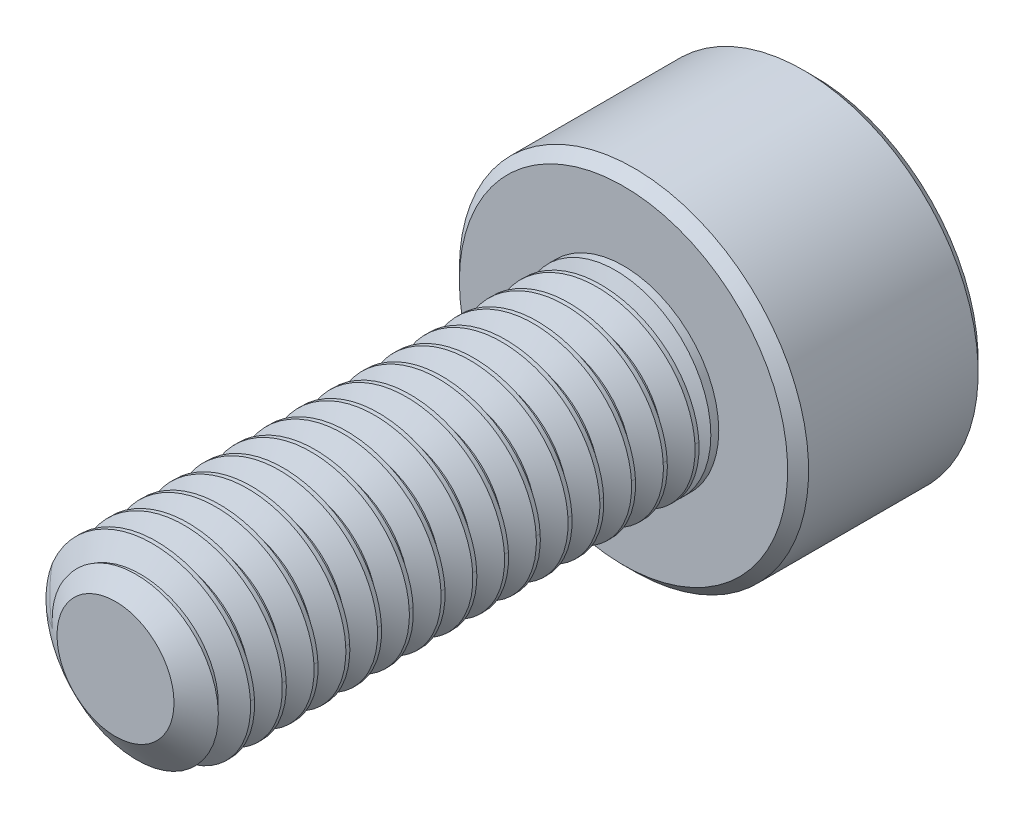
SolidWorks part; units mm, degrees
ref_plane "Front Plane" through (0, 0, 0) normal (0, 0, 1) x (1, 0, 0)
ref_plane "Top Plane" through (0, 0, 0) normal (0, 1, 0) x (1, 0, 0)
ref_plane "Right Plane" through (0, 0, 0) normal (1, 0, 0) x (0, 0, -1)
sketch "Sketch1" plane through (0, 0, 0) normal (0, 0, 1) x (1, 0, 0)
  circle A0 centre (0, 0) radius 1.5
  dimension "OD" = 3
extrude "Extrude1" add sketch "Sketch1" against normal blind 8
sketch "Sketch2" plane through (0, 0, 0) normal (0, 0, 1) x (1, 0, 0)
  circle A0 centre (0, 0) radius 1.5 construction
  circle A1 centre (0, 0) radius 1.5
curve "Helix/Spiral1" pitch 0.5 height 8.5 radius 1.5 centre (0, 0, 0) axis (0, 0, -1) start towards (0, 1, 0) parameters "pitch"=0.5
sketch "Sketch3" plane through (0, 0, 0) normal (1, 0, 0) x (0, 0, -1)
  line L0 (-0.4375, 1.5) -> (-0.25, 1.1752)
  line L1 (-0.25, 1.1752) -> (-0.1875, 1.1752)
  line L2 (-0.1875, 1.1752) -> (0, 1.5)
  line L3 (-0.4375, 1.5) -> (0, 1.5)
  line L4 (-0.2187, 1.5) -> (-0.2187, 1.1752) construction
  line L5 (-0.3437, 1.3376) -> (-0.0937, 1.3376) construction
  line L6 (0, 1.5) -> (0, -1.5) construction
  line L7 (0, -1.5) -> (8, -1.5) construction
  point P11 (2.25, -1.5)
  dimension "D1" = 0.0625
  dimension "D2" = 0.25
  dimension "D3" = 60
  dimension "D4" = 2.25
sweep "Cut-Sweep1" cut profiles "Sketch3" path "Helix/Spiral1"
sketch "Sketch4" plane through (0, 0, 0) normal (1, 0, 0) x (0, 0, -1)
  line L0 (0.4053, 1.5) -> (0, 0.9212)
  line L1 (0, 0.9212) -> (0, 1.5)
  line L2 (0.4053, 1.5) -> (0, 1.5)
  line L3 (-0.4375, 1.5) -> (0, 1.5) construction
  line L4 (0, 0) -> (7.0209, 0) construction
  dimension "D1" = 55
  dimension "D2" = 0.254
revolve "Cut-Revolve1" cut sketch "Sketch4" angle 360 about L4
sketch "Sketch5" plane through (0, 0, 0) normal (1, 0, 0) x (0, 0, -1)
  line L0 (8, -1.1822) -> (8, 1.0703) construction
  line L1 (8, 1.5) -> (0.1203, 1.5)
  line L2 (8, 1.5) -> (8, 0)
  line L3 (8, 0) -> (0.0001, 0)
  line L4 (0.0001, 1.1698) -> (0.0001, 0)
  line L5 (0.1203, 1.5) -> (0.0001, 1.1698)
  line L6 (0, 0) -> (9.9695, 0) construction
  point P3 (0.0001, 1.5)
  point P10 (0.0001, 1.5)
  dimension "D1" = 0.3302
  dimension "Thread min" = 0.0001
  dimension "D3" = 20
revolve "partially thread" [suppressed] add sketch "Sketch5" angle 360 about L6
sketch "Sketch6" plane through (0, 0, -8) normal (0, 0, -1) x (-1, 0, 0)
  circle A0 centre (0, 0) radius 2.75
  dimension "head dia" = 5.5
extrude "Extrude2" add sketch "Sketch6" along normal blind 3
sketch "Sketch7" plane through (0, 0, -11) normal (0, 0, -1) x (-1, 0, 0)
  line L1 (0, 1.4434) -> (-1.25, 0.7217)
  line L2 (-1.25, 0.7217) -> (-1.25, -0.7217)
  line L3 (-1.25, -0.7217) -> (0, -1.4434)
  line L4 (0, -1.4434) -> (1.25, -0.7217)
  line L5 (1.25, -0.7217) -> (1.25, 0.7217)
  line L6 (1.25, 0.7217) -> (0, 1.4434)
  circle A0 centre (0, 0) radius 1.25 construction
  dimension "hex dia" = 2.5
extrude "Cut-Extrude1" cut sketch "Sketch7" against normal blind 1.875
sketch "Sketch8" plane through (0, 0, -11) normal (0, 0, -1) x (-1, 0, 0)
  circle A0 centre (0, 0) radius 1.4434
extrude "Cut-Extrude2" cut sketch "Sketch8" against normal through all draft 45
chamfer "Chamfer1" distance 0.165 angle 45 2 edges at (-2.75, 0, -11) (-2.75, 0, -8)
sketch "Sketch9" plane through (0, 0, 0) normal (1, 0, 0) x (0, 0, -1)
  line L0 (0, 1.5) -> (0, -1.5) construction
  line L1 (2.75, 1.5) -> (2.75, -1.5) construction
  dimension "D1" = 2.75
sketch "Sketch10" plane through (0, 0, 0) normal (1, 0, 0) x (0, 0, -1)
  line L0 (8, 1.5) -> (8, 0)
  line L1 (8, 1.5) -> (7.875, 1.5)
  line L2 (7.875, 1.5) -> (7.2537, 0)
  line L3 (8, 0) -> (7.2537, 0)
  line L4 (8, 2.585) -> (8, -2.585) construction
  dimension "D1" = 22.5
  dimension "D2" = 0.125
revolve "Revolve1" add sketch "Sketch10" angle 360 about L3
equation "\"D3@Helix/Spiral1\" = \"screw length@Extrude1\"+\"pitch@Helix/Spiral1\""
equation "\"D1@Sketch3\" = \"pitch@Helix/Spiral1\"*.125"
equation "\"D2@Sketch3\" = \"pitch@Helix/Spiral1\"*.5"
equation "\"D1@Cut-Extrude1\" = \"hex dia@Sketch7\"*.75"
equation "\"D1@Chamfer1\" = \"head dia@Sketch6\"*.03"
equation "\"D1@Sketch9\" = \"pitch@Helix/Spiral1\"*5.5"
equation "\"D2@Sketch10\" = \"pitch@Helix/Spiral1\"*.25"
equation "\"D4@Sketch3\" = \"pitch@Helix/Spiral1\"*4.50"
